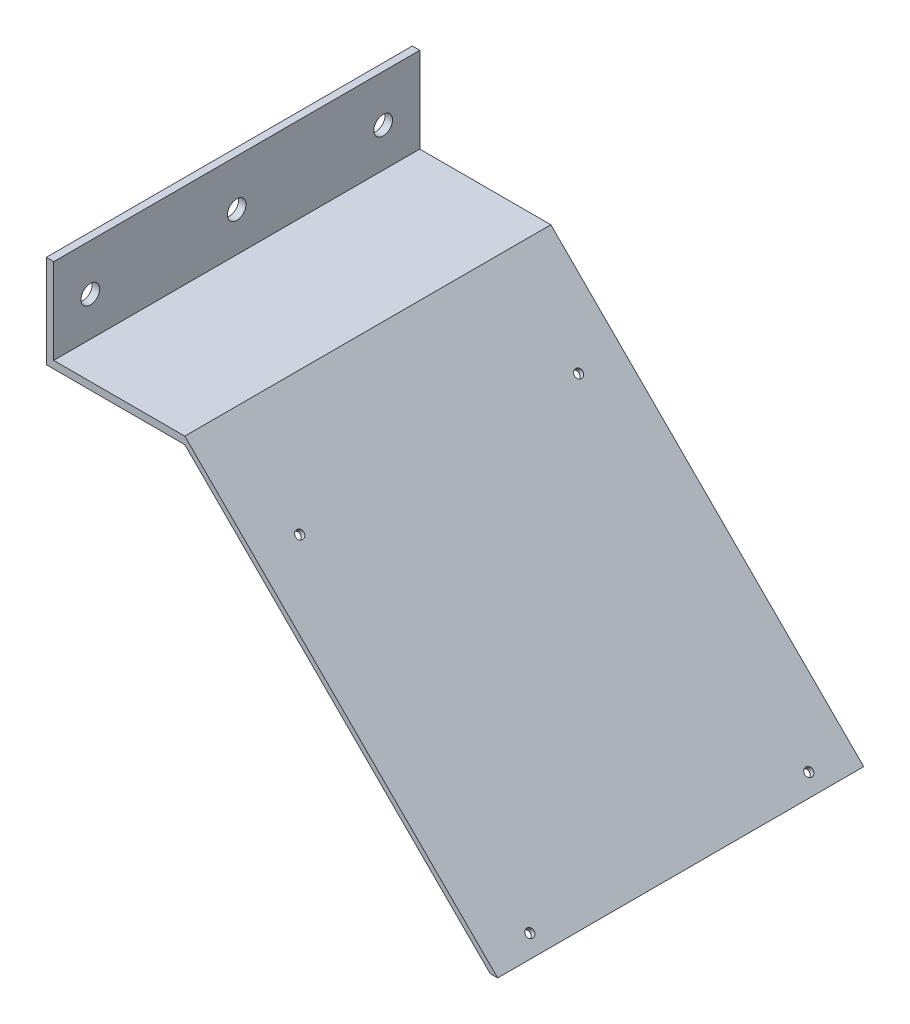
SolidWorks part; units mm, degrees
ref_plane "Front Plane" through (0, 0, 0) normal (0, 0, 1) x (1, 0, 0)
ref_plane "Top Plane" through (0, 0, 0) normal (0, 1, 0) x (1, 0, 0)
ref_plane "Right Plane" through (0, 0, 0) normal (1, 0, 0) x (0, 0, -1)
sketch "Sketch1" plane through (0, 0, 0) normal (0, 0, 1) x (1, 0, 0)
  line L0 (0, 0) -> (83.4386, -83.4386)
  line L9 (83.4386, -83.4386) -> (85.4706, -83.4386)
  line L10 (85.4706, -83.4386) -> (0, 2.032)
  line L12 (0, 2.032) -> (0, 0) construction
  line L13 (0, 0) -> (-37.8429, 0)
  line L14 (0, 0) -> (0, 2.032)
  line L15 (0, 2.032) -> (-37.8429, 2.032)
  line L16 (-37.8429, 0) -> (-37.8429, 2.032)
  line L17 (-37.8429, 0) -> (-35.8109, 0)
  line L18 (-37.8429, 0) -> (-37.8429, 25.4)
  line L19 (-37.8429, 25.4) -> (-35.8109, 25.4)
  line L20 (-35.8109, 0) -> (-35.8109, 25.4)
  line L21 (1.016, 1.016) -> (0, 0) construction
  dimension "D1" = 45
  dimension "D4" = 118
  dimension "D2" = 2.032
  dimension "D3" = 37.8429
  dimension "D5" = 25.4
  dimension "D7" = 1.4368
extrude "Boss-Extrude1" add sketch "Sketch1" along normal blind 100 contours L10 L12 L0 L9 | L20 L13 L14 L15 | L15 L20 L19 L18 | L13 L20 L15 L16 region at (42.2293, -41.2093, 0) region at (-17.9054, 1.016, 0) region at (-36.8269, 1.016, 0) region at (-36.8269, 13.716, 0)
sketch "Sketch2" plane through (1.016, 1.016, 0) normal (0.7071, 0.7071, 0) x (0, 0, -1)
  line L0 (-50, -28.0868) -> (-50, -113.0868) construction
  line L1 (-80, -28.0868) -> (-20, -28.0868) construction
  line L2 (-80, -28.0868) -> (-80, -113.0868) construction
  line L3 (-80, -113.0868) -> (-20, -113.0868) construction
  line L4 (-20, -28.0868) -> (-20, -113.0868) construction
  line L5 (-75, -35.1868) -> (-25, -35.1868) construction
  line L6 (-75, -35.1868) -> (-75, -105.9868) construction
  line L7 (-75, -105.9868) -> (-25, -105.9868) construction
  line L10 (-25, -35.1868) -> (-25, -105.9868) construction
  line L11 (-69.455, -33.8888) -> (-30.545, -33.8888) construction
  line L12 (-69.455, -33.8888) -> (-69.455, -107.2848) construction
  line L13 (-69.455, -107.2848) -> (-30.545, -107.2848) construction
  line L14 (-30.545, -33.8888) -> (-30.545, -107.2848) construction
  line L15 (-80, -70.5868) -> (-20, -70.5868) construction
  line L17 (-100, -119.4368) -> (0, -119.4368) construction
  line L19 (-100, -119.4368) -> (-100, 1.4368) construction
  line L21 (-88.1, -26.1368) -> (-88.1, -115.0368) construction
  line L22 (-88.1, -115.0368) -> (-11.9, -115.0368) construction
  line L23 (-11.9, -115.0368) -> (-11.9, -26.1368) construction
  line L24 (-11.9, -26.1368) -> (-88.1, -26.1368) construction
  circle A0 centre (-88.1, -26.1368) radius 1.13
  circle A1 centre (-11.9, -26.1368) radius 1.13
  circle A2 centre (-11.9, -115.0368) radius 1.13
  circle A3 centre (-88.1, -115.0368) radius 1.13
  point P6 (-25, -70.5868)
  point P10 (-50, -28.0868)
  point P13 (-50, -70.5868)
  point P17 (-50, -35.1868)
  point P23 (-50, -33.8888)
  point P24 (-30.545, -70.5868)
  point P37 (-50, -26.1368)
  point P39 (-11.9, -70.5868)
  dimension "D12" = 2.26
  dimension "D2" = 6.35
  dimension "D3" = 50
  dimension "D11" = 76.2
  dimension "D13" = 88.9
ref_axis "Axis1" through (-9.1341, -48.8964, 50) along (1, 0, 0)
extrude "Cut-Extrude1" cut sketch "Sketch2" against normal through all both and the other way through all
hole_wizard "#4-40 Tapped Hole1" positions "3DSketch1" profile "Sketch3" tap size "#4-40" standard "ANSI Inch" end condition through all
sketch3d "3DSketch1"
  point P0 (19.4975, -17.4655, 88.1)
  point P3 (19.4975, -17.4655, 11.9)
  point P6 (82.3593, -80.3273, 11.9)
  point P9 (82.3593, -80.3273, 88.1)
sketch "Sketch3" plane through (19.4975, -17.4655, 88.1) normal (0, 0, 1) x (-0.7071, 0.7071, 0)
  line L0 (0, 0) -> (0, 87.1958)
  line L1 (0, 87.1958) -> (1.1303, 87.1958)
  line L2 (1.1303, 87.1958) -> (1.1303, 0)
  line L5 (1.1303, 0) -> (0, 0)
  line L11 (0, -6.35) -> (0, 107.95) construction
  dimension "Thru Tap Drill Dia." = 2.2606
  dimension "Thru Tap Drill Depth" = 87.1958
cosmetic thread "Hole Thread1" parameters "D2"=2.8448
cosmetic thread "Hole Thread2" parameters "D2"=2.8448
cosmetic thread "Hole Thread3" parameters "D2"=2.8448
cosmetic thread "Hole Thread4" parameters "D2"=2.8448
hole_wizard "1/4-20 Tapped Hole1" positions "Sketch4" profile "Sketch5" tap size "1/4-20" standard "ANSI Inch" end condition through all
sketch "Sketch4" plane through (-37.8429, 0, 0) normal (-1, 0, 0) x (0, 0, 1)
  line L0 (10, 12.7) -> (50, 12.7) construction
  line L1 (50, 12.7) -> (90, 12.7) construction
  line L4 (0, 0) -> (0, 25.4) construction
  point P0 (10, 12.7)
  point P2 (50, 12.7)
  point P4 (90, 12.7)
  dimension "D1" = 80
  dimension "D2" = 10
  dimension "D3" = 12.7
sketch "Sketch5" plane through (-37.8429, 12.7, 10) normal (0, 1, 0) x (0, 0, 1)
  line L0 (0, 0) -> (0, 123.3135)
  line L1 (0, 123.3135) -> (2.5527, 123.3135)
  line L2 (2.5527, 123.3135) -> (2.5527, 0)
  line L5 (2.5527, 0) -> (0, 0)
  line L11 (0, -6.35) -> (0, 107.95) construction
  dimension "Thru Tap Drill Dia." = 5.1054
  dimension "Thru Tap Drill Depth" = 123.3135
cosmetic thread "Hole Thread5" parameters "D2"=6.35
cosmetic thread "Hole Thread6" parameters "D2"=6.35
cosmetic thread "Hole Thread7" parameters "D2"=6.35
equation "\"width\"=100"
equation "\"D1@Boss-Extrude1\"=\"width\""
equation "\"height\"=118"
equation "\"D4@Sketch1\"=\"height\""
equation "\"D3@Sketch2\"=100/2"
equation "\"D13@Sketch2\"=3.5*25.4"
equation "\"D11@Sketch2\"=3.0*25.4"
equation "\"D2@Sketch4\"=(100-\"D1@Sketch4\")/2"
